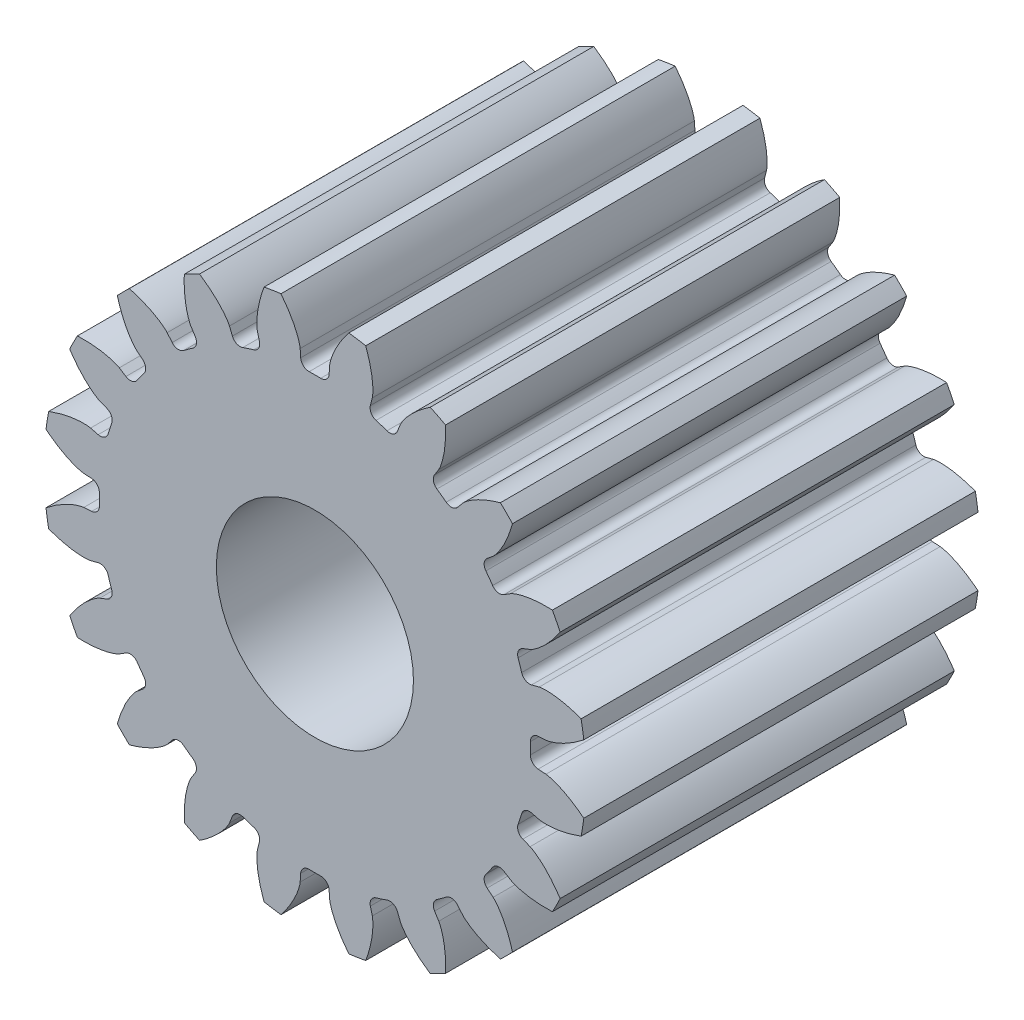
SolidWorks part; units mm, degrees
ref_plane "Front Plane" through (0, 0, 0) normal (0, 0, 1) x (1, 0, 0)
ref_plane "Top Plane" through (0, 0, 0) normal (0, 1, 0) x (1, 0, 0)
ref_plane "Right Plane" through (0, 0, 0) normal (1, 0, 0) x (0, 0, -1)
sketch "Sketch1" plane through (0, 0, 0) normal (0, 0, 1) x (1, 0, 0)
  line L0 (0, 0) -> (0, 7.9375) construction
  line L1 (-2.5511, 8.866) -> (2.5511, 7.009) construction
  circle A0 centre (0, 0) radius 6.9453 construction
  circle A1 centre (0, 0) radius 8.7312 construction
  circle A2 centre (0, 0) radius 7.9375 construction
  circle A3 centre (0, 0) radius 7.4588 construction
  point P8 (406.4, 0)
  point P13 (254, 0)
  dimension "OD | Outside Diameter" = 17.4625
  dimension "Root Diameter" = 13.8906
  dimension "Gear Pitch Diameter" = 15.875
  dimension "Base Diameter" = 14.9176
  dimension "Pressure Angle" = 20
  dimension "Number of Teeth" = 508
  dimension "Gear Pitch | Diametral Pitch" = 812.8
sketch "Sketch2" plane through (0, 0, 0) normal (1, 0, 0) x (0, 0, -1)
  line L0 (-6.35, 0) -> (6.35, 0) construction
  point P2 (2.3812, 0)
  point P5 (6.7469, 0)
  point P6 (-2.3812, 0)
  dimension "Length" = 12.7
  dimension "D1" = 8.7312
  dimension "D2" = 13.0969
  dimension "D3" = 8.7312
sketch "Sketch3" plane through (0, 0, 0) normal (0, 0, 1) x (1, 0, 0)
  circle A0 centre (0, 0) radius 8.7312
  circle A1 centre (0, 0) radius 8.7312 construction
extrude "Boss-Extrude1" add sketch "Sketch3" against normal up to vertex (6.35 mm away) and the other way up to vertex (6.35 mm away) up to point (0, 0, -6.35) other way up to point (0, 0, 6.35)
sketch "Sketch4" plane through (0, 0, 0) normal (0, 0, 1) x (1, 0, 0)
  line L0 (0, 0) -> (6.9313, 0.4417) construction
  line L2 (0, 0) -> (6.9313, -0.4417) construction
  line L4 (6.9313, 0.4417) -> (7.4437, 0.4743)
  line L5 (7.4437, -0.4743) -> (6.9313, -0.4417)
  arc A0 (6.9313, 0.4417) -> (6.9313, -0.4417) centre (0, 0) cw
  arc A3 (8.6626, 1.0928) -> (8.6626, -1.0928) centre (0, 0) cw
  circle A4 centre (0, 0) radius 8.7312 construction
  spline S0 degree 4 poles (7.4437, 0.4743) (7.4457, 0.4745) (7.4515, 0.475) (7.4622, 0.4763) (7.4797, 0.4789) (7.502, 0.4828) (7.5306, 0.4887) (7.5643, 0.4966) (7.6011, 0.5063) (7.6409, 0.518) (7.6805, 0.5306) (7.7199, 0.5441) (7.7589, 0.5584) (7.806, 0.5766) (7.8621, 0.5998) (7.9274, 0.6288) (8.0008, 0.664) (8.0749, 0.7023) (8.1474, 0.742) (8.22, 0.7844) (8.2897, 0.8269) (8.3615, 0.8734) (8.4273, 0.9176) (8.5003, 0.9695) (8.5589, 1.0122) (8.6353, 1.0711) (8.6802, 1.1067) (8.7324, 1.1493) (8.7553, 1.1687) (8.7695, 1.1806) knots 0 0 0 0 0 0.005377 0.015084 0.028532 0.04661 0.064855 0.092111 0.119476 0.146842 0.174209 0.201575 0.228941 0.256307 0.307035 0.361767 0.4165 0.471232 0.525964 0.580697 0.635429 0.690161 0.744894 0.799626 0.854358 0.909091 0.954545 1 1 1 1 1 construction
  spline S1 degree 4 poles (7.4437, 0.4743) (7.4457, 0.4745) (7.4515, 0.475) (7.4622, 0.4763) (7.4797, 0.4789) (7.502, 0.4828) (7.5306, 0.4887) (7.5643, 0.4966) (7.6011, 0.5063) (7.6409, 0.518) (7.6805, 0.5306) (7.7199, 0.5441) (7.7589, 0.5584) (7.806, 0.5766) (7.8621, 0.5998) (7.9274, 0.6288) (8.0008, 0.664) (8.0749, 0.7023) (8.1474, 0.742) (8.22, 0.7844) (8.2897, 0.8269) (8.3615, 0.8734) (8.4273, 0.9176) (8.5003, 0.9695) (8.5589, 1.0122) (8.6188, 1.0583) (8.6478, 1.0811) (8.6626, 1.0928) knots 0 0 0 0 0 0.005377 0.015084 0.028532 0.04661 0.064855 0.092111 0.119476 0.146842 0.174209 0.201575 0.228941 0.256307 0.307035 0.361767 0.4165 0.471232 0.525964 0.580697 0.635429 0.690161 0.744894 0.799626 0.854358 0.909091 0.909091 0.909091 0.909091 0.909091
  spline S2 degree 4 poles (7.4437, -0.4743) (7.4457, -0.4745) (7.4515, -0.475) (7.4622, -0.4763) (7.4797, -0.4789) (7.502, -0.4828) (7.5306, -0.4887) (7.5643, -0.4966) (7.6011, -0.5063) (7.6409, -0.518) (7.6805, -0.5306) (7.7199, -0.5441) (7.7589, -0.5584) (7.806, -0.5766) (7.8621, -0.5998) (7.9274, -0.6288) (8.0008, -0.664) (8.0749, -0.7023) (8.1474, -0.742) (8.22, -0.7844) (8.2897, -0.8269) (8.3615, -0.8734) (8.4273, -0.9176) (8.5003, -0.9695) (8.5589, -1.0122) (8.6353, -1.0711) (8.6802, -1.1067) (8.7324, -1.1493) (8.7553, -1.1687) (8.7695, -1.1806) knots 0 0 0 0 0 0.005377 0.015084 0.028532 0.04661 0.064855 0.092111 0.119476 0.146842 0.174209 0.201575 0.228941 0.256307 0.307035 0.361767 0.4165 0.471232 0.525964 0.580697 0.635429 0.690161 0.744894 0.799626 0.854358 0.909091 0.954545 1 1 1 1 1 construction
  spline S3 degree 4 poles (7.4437, -0.4743) (7.4457, -0.4745) (7.4515, -0.475) (7.4622, -0.4763) (7.4797, -0.4789) (7.502, -0.4828) (7.5306, -0.4887) (7.5643, -0.4966) (7.6011, -0.5063) (7.6409, -0.518) (7.6805, -0.5306) (7.7199, -0.5441) (7.7589, -0.5584) (7.806, -0.5766) (7.8621, -0.5998) (7.9274, -0.6288) (8.0008, -0.664) (8.0749, -0.7023) (8.1474, -0.742) (8.22, -0.7844) (8.2897, -0.8269) (8.3615, -0.8734) (8.4273, -0.9176) (8.5003, -0.9695) (8.5589, -1.0122) (8.6188, -1.0583) (8.6478, -1.0811) (8.6626, -1.0928) knots 0 0 0 0 0 0.005377 0.015084 0.028532 0.04661 0.064855 0.092111 0.119476 0.146842 0.174209 0.201575 0.228941 0.256307 0.307035 0.361767 0.4165 0.471232 0.525964 0.580697 0.635429 0.690161 0.744894 0.799626 0.854358 0.909091 0.909091 0.909091 0.909091 0.909091
  dimension "D1" = 13.8906
extrude "Cut-Extrude1" cut sketch "Sketch4" against normal through all both and the other way through all
fillet "Fillet1" radius 0.2663 2 edges at (6.9313, -0.4417, 0) (6.9313, 0.4417, 0)
pattern_circular "CirPattern1" count 20 over 360 about axis through (0, 0, 6.35) along (0, 0, -1) of "Cut-Extrude1", "Fillet1"
sketch "Sketch5" plane through (0, 0, 6.35) normal (0, 0, 1) x (1, 0, 0)
  point P0 (0, 0)
hole_wizard "1/4 (0.2500) Dowel Hole1" positions "Sketch5" profile "Sketch6" hole size "1/4" standard "ANSI Inch" end condition through all
sketch "Sketch6" plane through (0, 0, 6.35) normal (1, 0, 0) x (0, -1, 0)
  line L0 (0, 0) -> (0, 12.7)
  line L1 (0, 12.7) -> (3.175, 12.7)
  line L2 (3.175, 12.7) -> (3.175, 0)
  line L5 (3.175, 0) -> (0, 0)
  line L11 (0, -6.35) -> (0, 107.95) construction
  dimension "Thru Hole Dia." = 6.35
  dimension "Thru Hole Depth" = 12.7
equation "\"Root Diameter@Sketch1\"=\"Root Diameter\""
equation "\"OD | Outside Diameter@Sketch1\"=\"Outside Diameter\""
equation "\"D1@CirPattern1\"=\"Number of Teeth\""
equation "\"Diametral Pitch\"=32"
equation "\"Number of Teeth\"= 20"
equation "\"Pressure Angle\"=20"
equation "\"Pitch Diameter\"= \"Number of Teeth\" / \"Diametral Pitch\""
equation "\"Base Diameter\"= \"Pitch Diameter\" * cos ( \"Pressure Angle\" )"
equation "\"Outside Diameter\"= ( \"Number of Teeth\" + 2 ) / \"Diametral Pitch\""
equation "\"Dedendum\"= 1.25 / \"Diametral Pitch\""
equation "\"Root Diameter\"= \"Pitch Diameter\" - ( 2 * \"Dedendum\" )"
equation "\"Pitch Angle\"= 360deg / \"Number of Teeth\""
equation "\"Alpha\"= sqr ( \"Pitch Diameter\" ^ 2 - \"Base Diameter\" ^ 2 ) / \"Base Diameter\" * 180 / PI - \"Pressure Angle\""
equation "\"Beta\"= ( \"Pitch Angle\" / 4 - \"Alpha\" )"
equation "\"Phi\"= sqr ( ( \"Outside Diameter\" / 2 ) ^ 2 - ( \"Base Diameter\" / 2 ) ^ 2 ) / ( \"Base Diameter\" / 2 )"
equation "\"Addendum\"= 1 / \"Diametral Pitch\""
equation "\"WorkingDepth\"= 2 / \"Diametral Pitch\""
equation "\"WholeDepth\"= 2.25 / \"Diametral Pitch\""
equation "\"Clearance\"= 0.25 / \"Diametral Pitch\""
equation "\"ToothThickness\"= ( pi * 2 ) / \"Diametral Pitch\""
equation "\"CircularPitch\"= pi / \"Diametral Pitch\""
equation "\"Number of Teeth@Sketch1\"=\"Number of Teeth\""
equation "\"Gear Pitch | Diametral Pitch@Sketch1\"=\"Diametral Pitch\""
equation "\"Pressure Angle@Sketch1\"=\"Pressure Angle\""
equation "\"Gear Pitch Diameter@Sketch1\"=\"Pitch Diameter\""
equation "\"Base Diameter@Sketch1\"=\"Base Diameter\""
equation "\"Fillet\"= \"Clearance\" * cos ( \"Pressure Angle\" ) * tan ( ( 90 + \"Pressure Angle\" ) / 2 )"
equation "\"D1@Fillet1\"=\"Fillet\""
equation "\"D1@Sketch4\"=if( \"Base Diameter\">\"Root Diameter\",\"Root Diameter\",\"Base Diameter\"-.00001)"
equation "\"D1@Sketch2\"=\"OD | Outside Diameter@Sketch1\"*2*0.5*0.5"
equation "\"D2@Sketch2\"=\"D1@Sketch2\"*1.5"
equation "\"D3@Sketch2\"=\"D1@Sketch2\""
equation "\"Length\"= .5in"
equation "\"Length@Sketch2\"= \"Length\""
